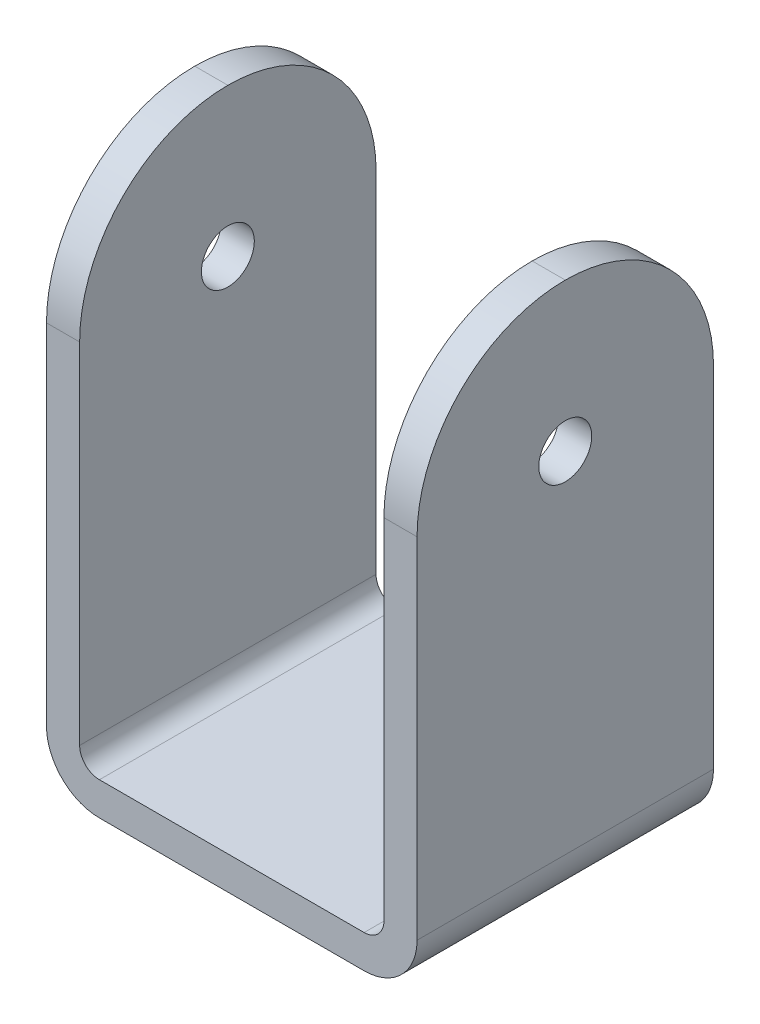
SolidWorks part; units mm, degrees
ref_plane "Front Plane" through (0, 0, 0) normal (0, 0, 1) x (1, 0, 0)
ref_plane "Top Plane" through (0, 0, 0) normal (0, 1, 0) x (1, 0, 0)
ref_plane "Right Plane" through (0, 0, 0) normal (1, 0, 0) x (0, 0, -1)
sketch "Sketch1" plane through (0, 0, 0) normal (0, 0, 1) x (1, 0, 0)
  line L0 (-144.8227, 103.1155) -> (-144.8227, -16.2645)
  line L1 (-132.1227, -28.9645) -> (-68.6227, -28.9645)
  line L2 (-55.9227, -16.2645) -> (-55.9227, 103.1155)
  line L3 (-136.8725, 103.1155) -> (-136.8725, -16.2645)
  line L4 (-132.1227, -21.0143) -> (-68.6227, -21.0143)
  line L5 (-63.8729, -16.2645) -> (-63.8729, 103.1155)
  line L6 (-144.8227, 103.1155) -> (-136.8725, 103.1155)
  line L7 (-63.8729, 103.1155) -> (-55.9227, 103.1155)
  arc A0 (-68.6227, -28.9645) -> (-55.9227, -16.2645) centre (-68.6227, -16.2645) ccw
  arc A1 (-144.8227, -16.2645) -> (-132.1227, -28.9645) centre (-132.1227, -16.2645) ccw
  arc A2 (-136.8725, -16.2645) -> (-132.1227, -21.0143) centre (-132.1227, -16.2645) ccw
  arc A3 (-68.6227, -21.0143) -> (-63.8729, -16.2645) centre (-68.6227, -16.2645) ccw
  point P8 (-55.9227, -28.9645)
  point P11 (-144.8227, -28.9645)
  dimension "D4" = 12.7
  dimension "D1" = 132.08
  dimension "D2" = 132.08
  dimension "D3" = 88.9
  dimension "D5" = 7.9502
extrude "Boss-Extrude3" add sketch "Sketch1" along normal blind 71.12
fillet "Fillet3" radius 35.56 4 edges at (-59.8978, 103.1155, 71.12) (-59.8978, 103.1155, 0) (-140.8476, 103.1155, 0) (-140.8476, 103.1155, 71.12)
sketch "Sketch6" plane through (-55.9227, 0, 0) normal (1, 0, 0) x (0, 0, -1)
  circle A0 centre (-35.56, 67.5555) radius 6.35
  dimension "D1" = 12.7
extrude "Cut-Extrude1" cut sketch "Sketch6" against normal through all
